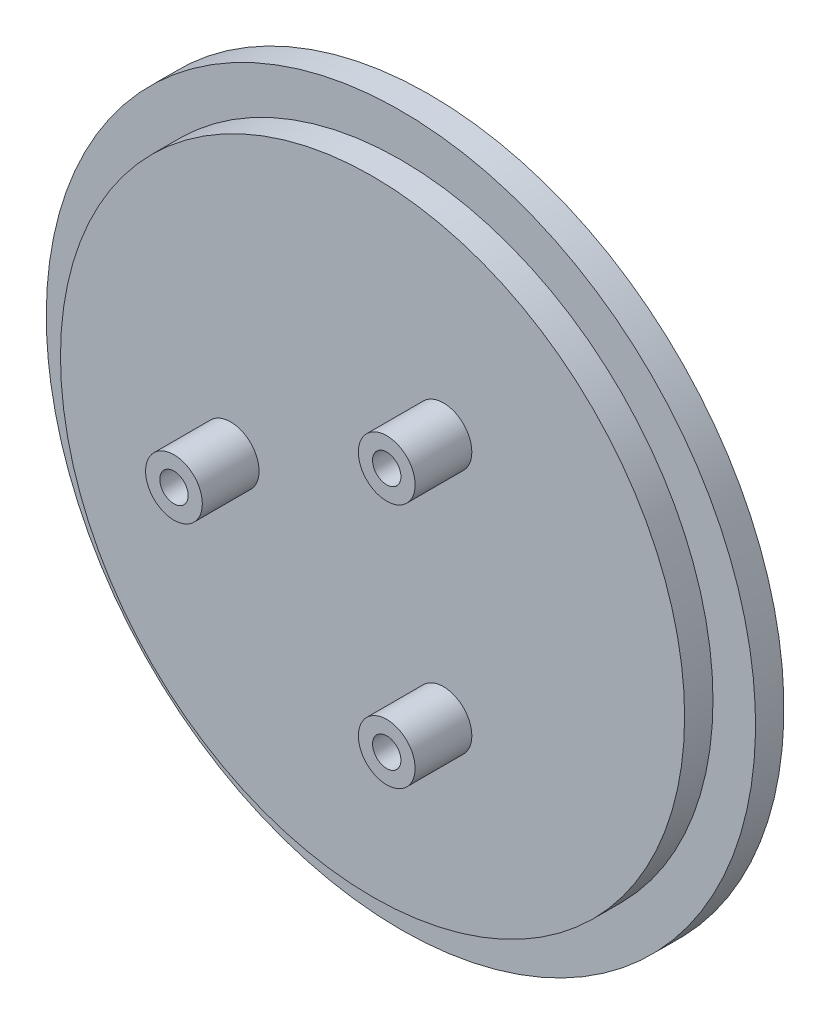
SolidWorks part; units mm, degrees
ref_plane "前视基准面" through (0, 0, 0) normal (0, 0, 1) x (1, 0, 0)
ref_plane "上视基准面" through (0, 0, 0) normal (0, 1, 0) x (1, 0, 0)
ref_plane "右视基准面" through (0, 0, 0) normal (1, 0, 0) x (0, 0, -1)
sketch "草图1" plane through (0, 0, 0) normal (0, 0, 1) x (1, 0, 0)
  circle A0 centre (0, 0) radius 22
extrude "凸台-拉伸1" add sketch "草图1" along normal blind 2
sketch "草图2" plane through (0, 0, 2) normal (0, 0, 1) x (1, 0, 0)
  circle A1 centre (-10, 0) radius 1
  circle A2 centre (5, -8.6603) radius 1
  circle A3 centre (5, 8.6603) radius 1
  circle A4 centre (-10, 0) radius 2
  circle A5 centre (5, 8.6603) radius 2
  circle A6 centre (5, -8.6603) radius 2
extrude "凸台-拉伸2" add sketch "草图2" along normal blind 4
sketch "草图3" plane through (0, 0, 0) normal (0, 0, -1) x (-1, 0, 0)
  circle A0 centre (0, 0) radius 25
extrude "凸台-拉伸3" add sketch "草图3" along normal blind 2
sketch "草图4" plane through (0, 0, -2) normal (0, 0, -1) x (-1, 0, 0)
  line L1 (-7.25, 3.95) -> (7.25, 3.95)
  line L3 (-7.25, -3.95) -> (7.25, -3.95)
  arc A2 (-7.25, 3.95) -> (-7.25, -3.95) centre (-7.25, 0) ccw
  arc A3 (7.25, 3.95) -> (7.25, -3.95) centre (7.25, 0) cw
  point P8 (0, 3.95)
  point P11 (0, -3.95)
extrude "切除-拉伸1" cut sketch "草图4" against normal blind 2
sketch "草图5" plane through (0, 0, -2) normal (0, 0, -1) x (-1, 0, 0)
  line L8 (28.3015, -3.95) -> (28.3015, 3.95)
  line L9 (21, 3.95) -> (28.3015, 3.95)
  line L10 (21, -3.95) -> (21, 3.95)
  line L11 (21, -3.95) -> (28.3015, -3.95)
extrude "切除-拉伸2" cut sketch "草图5" against normal blind 1
